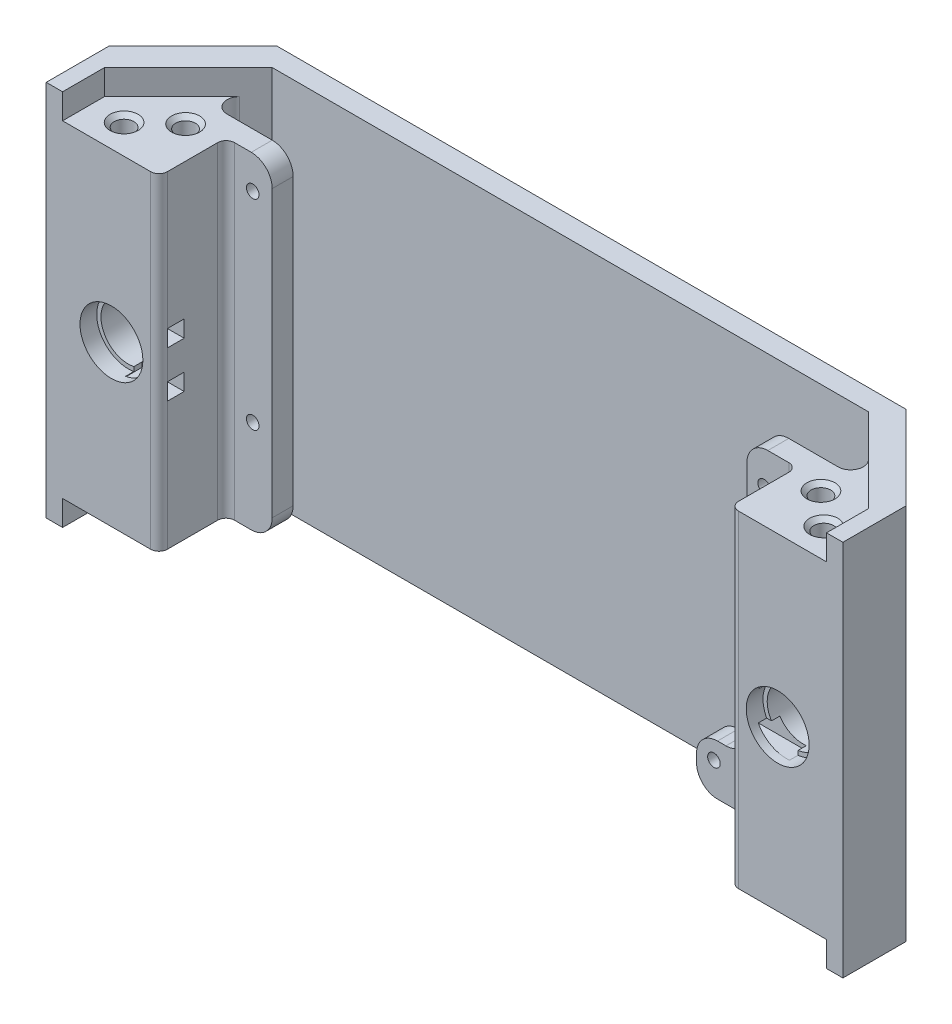
SolidWorks part; units mm, degrees
ref_plane "Front Plane" through (0, 0, 0) normal (0, 0, 1) x (1, 0, 0)
ref_plane "Top Plane" through (0, 0, 0) normal (0, 1, 0) x (1, 0, 0)
ref_plane "Right Plane" through (0, 0, 0) normal (1, 0, 0) x (0, 0, -1)
sketch "Sketch1" plane through (0, 0, 0) normal (0, 0, 1) x (1, 0, 0)
  line L1 (-95, 45) -> (95, 45)
  line L2 (-95, 45) -> (-95, -45)
  line L3 (-95, -45) -> (95, -45)
  line L4 (95, 45) -> (95, -45)
  line L5 (-95, 45) -> (95, -45) construction
  line L6 (-95, -45) -> (95, 45) construction
  point P0 (0, 0)
  point P6 (0, 0)
  dimension "D2" = 190
  dimension "D4" = 90
extrude "Boss-Extrude1" add sketch "Sketch1" along normal blind 5
sketch "Sketch2" plane through (0, 0, 5) normal (0, 0, 1) x (1, 0, 0)
  line L0 (-95, -45) -> (95, -45) construction
  line L1 (-95, 45) -> (-91.1, 45)
  line L2 (-95, 45) -> (-95, -45)
  line L3 (-95, -45) -> (-91.1, -45)
  line L4 (-91.1, 45) -> (-91.1, -45)
  line L5 (0, 0) -> (0, 45) construction
  line L6 (95, 45) -> (-95, 45) construction
  line L7 (95, -45) -> (91.1, -45)
  line L8 (91.1, 45) -> (91.1, -45)
  line L9 (95, 45) -> (91.1, 45)
  line L10 (95, 45) -> (95, -45)
  dimension "D1" = 3.9
extrude "Boss-Extrude2" add sketch "Sketch2" along normal blind 30
sketch "Sketch3" plane through (0, 45, 0) normal (0, 1, 0) x (1, 0, 0)
  line L0 (-91.1, -35) -> (-91.1, -5) construction
  line L1 (-91.1, -14) -> (-57.1, -14)
  line L2 (-91.1, -14) -> (-91.1, -19)
  line L3 (-91.1, -19) -> (-57.1, -19)
  line L4 (-57.1, -14) -> (-57.1, -19)
  line L5 (91.1, -35) -> (91.1, -5) construction
  line L6 (91.1, -14) -> (44.1, -14)
  line L7 (91.1, -14) -> (91.1, -19)
  line L8 (91.1, -19) -> (44.1, -19)
  line L9 (44.1, -14) -> (44.1, -19)
  line L10 (91.1, -5) -> (-91.1, -5) construction
  dimension "D1" = 9
  dimension "D2" = 9
  dimension "D3" = 5
  dimension "D4" = 5
  dimension "D5" = 34
  dimension "D6" = 47
extrude "Boss-Extrude3" add sketch "Sketch3" against normal up to surface (90 mm away) up to face at (0, -45, 18.75)
sketch "Sketch4" plane through (0, 0, 19) normal (0, 0, 1) x (1, 0, 0)
  line L0 (91.1, -45) -> (91.1, 45) construction
  line L1 (-91.1, 45) -> (91.1, 45)
  line L2 (-91.1, 45) -> (-91.1, 39)
  line L3 (-91.1, 39) -> (91.1, 39)
  line L4 (91.1, 45) -> (91.1, 39)
  line L5 (0, 0) -> (-91.1, 0) construction
  line L6 (-91.1, -45) -> (-91.1, 45) construction
  line L7 (-91.1, -39) -> (91.1, -39)
  line L8 (91.1, -45) -> (91.1, -39)
  line L9 (-91.1, -45) -> (91.1, -45)
  line L10 (-91.1, -45) -> (-91.1, -39)
  dimension "D1" = 6
extrude "Cut-Extrude1" cut sketch "Sketch4" against normal blind 5
sketch "Sketch5" plane through (0, 0, 19) normal (0, 0, 1) x (1, 0, 0)
  line L0 (0, 0) -> (-61.75, 0) construction
  line L1 (-70.2, 37.38) -> (70.2, 37.38) construction
  line L2 (-70.2, 37.38) -> (-70.2, -37.38) construction
  line L3 (-70.2, -37.38) -> (70.2, -37.38) construction
  line L4 (70.2, 37.38) -> (70.2, -37.38) construction
  line L5 (-70.2, 37.38) -> (70.2, -37.38) construction
  line L6 (-70.2, -37.38) -> (70.2, 37.38) construction
  line L7 (-61.75, 0) -> (-61.75, 31.13) construction
  line L8 (-61.75, 0) -> (-61.75, -16.61) construction
  line L9 (48.25, 0) -> (60.23, 0) construction
  line L10 (60.23, 0) -> (60.23, 31.13) construction
  line L11 (0, 0) -> (48.25, 0) construction
  line L12 (48.25, 0) -> (48.25, -31.38) construction
  circle A0 centre (-61.75, 31.13) radius 1.5
  circle A1 centre (-61.75, -16.61) radius 1.5
  circle A2 centre (60.23, 31.13) radius 1.5
  circle A3 centre (48.25, -31.38) radius 1.5
  point P0 (0, 0)
  dimension "D10" = 3
  dimension "D11" = 3
  dimension "D12" = 3
  dimension "D13" = 3
  dimension "D1" = 140.4
  dimension "D2" = 74.76
  dimension "D3" = 61.75
  dimension "D4" = 31.13
  dimension "D5" = 16.61
  dimension "D6" = 60.23
  dimension "D7" = 31.13
  dimension "D8" = 48.25
  dimension "D9" = 31.38
extrude "Cut-Extrude2" cut sketch "Sketch5" against normal up to surface (5 mm away) up to face at (67.6, 0, 14)
sketch "Sketch6" plane through (0, 0, 19) normal (0, 0, 1) x (1, 0, 0)
  line L1 (44.1, 39) -> (56.1, 39)
  line L2 (44.1, 39) -> (44.1, -27)
  line L3 (44.1, -27) -> (56.1, -27)
  line L4 (56.1, 39) -> (56.1, -27)
  dimension "D1" = 12
  dimension "D2" = 66
extrude "Cut-Extrude3" cut sketch "Sketch6" against normal up to surface (5 mm away) up to face at (46.75, -31.38, 14)
chamfer "Chamfer6" distance 20 angle 45 4 edges at (91.1, 0, 5) (95, 0, 0) (-95, 0, 0) (-91.1, 0, 5)
sketch "Sketch7" plane through (0, 39, 0) normal (0, 1, 0) x (1, 0, 0)
  line L0 (-85.1, -19) -> (-91.1, -25)
  line L1 (-91.1, -25) -> (-91.1, -35)
  line L2 (-91.1, -35) -> (-68.1, -35)
  line L3 (-68.1, -35) -> (-68.1, -19)
  line L4 (-85.1, -19) -> (-57.1, -19) construction
  line L5 (-68.1, -19) -> (-85.1, -19)
  line L6 (0, 0) -> (0, -5) construction
  line L7 (71.1, -5) -> (-71.1, -5) construction
  line L8 (68.1, -35) -> (68.1, -19)
  line L9 (91.1, -35) -> (68.1, -35)
  line L10 (91.1, -25) -> (91.1, -35)
  line L11 (85.1, -19) -> (91.1, -25)
  line L12 (68.1, -19) -> (85.1, -19)
  dimension "D1" = 23
extrude "Boss-Extrude4" add sketch "Sketch7" against normal up to surface (78 mm away) up to face at (-69.85, -39, 16.5)
fillet "Fillet4" radius 5 6 edges at (-57.1, -39, 16.5) (-57.1, 39, 16.5) (56.1, 39, 16.5) (44.1, -39, 16.5) (44.1, -27, 16.5) (56.1, -27, 16.5)
fillet "Fillet5" radius 2 4 edges at (-68.1, 0, 35) (68.1, 0, 35) (68.1, 0, 19) (-68.1, 0, 19)
fillet "Fillet6" radius 3 2 edges at (-80.1, 0, 14) (80.1, 0, 14)
sketch "Sketch9" plane through (0, 0, 35) normal (0, 0, 1) x (1, 0, 0)
  line L6 (0, 0) -> (0, -45) construction
  line L7 (-71.1, -45) -> (71.1, -45) construction
  line L8 (-95, 45) -> (-95, -45) construction
  line L9 (-95, 39) -> (-79.45, 39) construction
  line L10 (-95, 39) -> (-95, -0.9074) construction
  line L11 (-95, -0.9074) -> (-79.45, -0.9074) construction
  line L12 (-79.45, 39) -> (-79.45, -0.9074) construction
  line L13 (-91.1, 39) -> (-70.1, 39) construction
  circle A0 centre (-79.45, -0.9074) radius 6.5
  circle A1 centre (79.45, -0.9074) radius 6.5
  dimension "D3" = 13
  dimension "D1" = 39.9074
  dimension "D2" = 15.55
extrude "Cut-Extrude4" cut sketch "Sketch9" against normal blind 10
sketch "Sketch10" plane through (0, 0, 35) normal (0, 0, 1) x (1, 0, 0)
  circle A0 centre (-79.45, -0.9074) radius 7.5
  circle A1 centre (79.45, -0.9074) radius 7.5
  dimension "D1" = 15
  dimension "D2" = 15
extrude "Cut-Extrude5" cut sketch "Sketch10" against normal blind 4
sketch "Sketch12" plane through (-68.1, 0, 0) normal (1, 0, 0) x (0, 0, -1)
  line L0 (-33, -4.4074) -> (-29, -4.4074)
  line L1 (-33, 39) -> (-23, 39) construction
  line L2 (-33, 39) -> (-33, -0.9074) construction
  line L3 (-33, -0.9074) -> (-23, -0.9074) construction
  line L4 (-23, 39) -> (-23, -0.9074) construction
  line L5 (-33, 6.5926) -> (-23, 6.5926) construction
  line L6 (-33, 6.5926) -> (-33, -8.4074) construction
  line L7 (-33, -8.4074) -> (-23, -8.4074) construction
  line L8 (-23, 6.5926) -> (-23, -8.4074) construction
  line L9 (-33, 6.5926) -> (-23, -8.4074) construction
  line L10 (-33, -8.4074) -> (-23, 6.5926) construction
  line L11 (-33, 6.5926) -> (-29, 6.5926)
  line L12 (-33, 6.5926) -> (-33, 2.5926)
  line L13 (-33, 2.5926) -> (-29, 2.5926)
  line L14 (-29, 6.5926) -> (-29, 2.5926)
  line L15 (-29, -8.4074) -> (-29, -4.4074)
  line L16 (-33, -8.4074) -> (-29, -8.4074)
  line L17 (-33, -8.4074) -> (-33, -4.4074)
  point P5 (-28, -0.9074)
  dimension "D1" = 39.9074
  dimension "D2" = 10
  dimension "D3" = 15
  dimension "D4" = 10
  dimension "D5" = 4
  dimension "D6" = 4
extrude "Cut-Extrude6" cut sketch "Sketch12" against normal blind 10 and the other way blind 148.4
sketch "Sketch15" plane through (0, 39, 0) normal (0, 1, 0) x (1, 0, 0)
  line L0 (68.1, -21) -> (68.1, -33) construction
  line L5 (72.8574, -14) -> (61.1, -14) construction
  line L6 (91.1, -35) -> (68.1, -35) construction
  line L7 (91.1, -35) -> (91.1, -14) construction
  line L8 (91.1, -14) -> (68.1, -14) construction
  line L9 (68.1, -35) -> (68.1, -14) construction
  line L10 (68.1, -14) -> (75.7667, -21) construction
  line L11 (75.7667, -21) -> (83.4333, -28) construction
  line L12 (83.4333, -28) -> (91.1, -35) construction
  line L13 (0, 0) -> (0, -5) construction
  line L14 (71.1, -5) -> (-71.1, -5) construction
  circle A0 centre (75.7667, -21) radius 2.35
  circle A1 centre (83.4333, -28) radius 2.35
  circle A2 centre (-75.7667, -21) radius 2.35
  circle A3 centre (-83.4333, -28) radius 2.35
  dimension "D1" = 4.7
  dimension "D2" = 4.7
  dimension "D3" = 23
  dimension "D4" = 21
extrude "Cut-Extrude7" cut sketch "Sketch15" against normal blind 8
chamfer "Chamfer7" distance 1 angle 45 4 edges at (-83.4333, 39, 25.65) (-75.7667, 39, 18.65) (83.4333, 39, 30.35) (75.7667, 39, 23.35)
sketch "Sketch17" plane through (0, -39, 0) normal (0, -1, 0) x (1, 0, 0)
  line L0 (0, 0) -> (0, 5) construction
  line L1 (91.1, 35) -> (68.1, 35) construction
  line L2 (91.1, 35) -> (91.1, 19) construction
  line L3 (91.1, 19) -> (68.1, 19) construction
  line L4 (68.1, 35) -> (68.1, 19) construction
  line L5 (-71.1, 5) -> (71.1, 5) construction
  line L6 (68.1, 33) -> (68.1, 21) construction
  line L7 (66.1, 19) -> (49.1, 19) construction
  circle A0 centre (79.6, 27) radius 6.1
  circle A1 centre (-79.6, 27) radius 6.1
  dimension "D2" = 12.2
  dimension "D1" = 11.5
  dimension "D3" = 8
  dimension "D4" = 11.5
extrude "Cut-Extrude8" cut sketch "Sketch17" against normal blind 3.2
fillet "Fillet7" radius 0.2 2 edges at (-85.7, -39, 27) (85.7, -39, 27)
